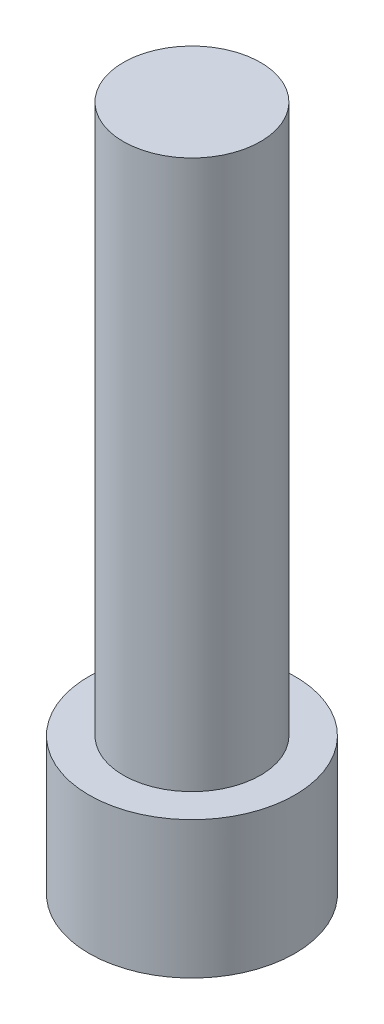
SolidWorks part; units mm, degrees
ref_plane "Front Plane" through (0, 0, 0) normal (0, 0, 1) x (1, 0, 0)
ref_plane "Top Plane" through (0, 0, 0) normal (0, 1, 0) x (1, 0, 0)
ref_plane "Right Plane" through (0, 0, 0) normal (1, 0, 0) x (0, 0, -1)
sketch "Sketch1" plane through (0, 0, 0) normal (0, 1, 0) x (1, 0, 0)
  line L1 (5.7735, 0) -> (2.8868, 5)
  line L2 (2.8868, 5) -> (-2.8868, 5)
  line L3 (-2.8868, 5) -> (-5.7735, 0)
  line L4 (-5.7735, 0) -> (-2.8868, -5)
  line L5 (-2.8868, -5) -> (2.8868, -5)
  line L6 (2.8868, -5) -> (5.7735, 0)
  circle A0 centre (0, 0) radius 5
  circle A1 centre (0, 0) radius 7.5
  circle A2 centre (0, 0) radius 5 construction
  point P4 (0, 0)
  dimension "D1" = 10
  dimension "D2" = 15
  dimension "D3" = 10
extrude "Boss-Extrude1" add sketch "Sketch1" along normal blind 40 contours A0 region at (0, 0, 0)
extrude "Boss-Extrude2" add sketch "Sketch1<3>" against normal blind 3 contours A0 L4 L5 | A0 L5 L6 | A0 L6 L1 | A0 L1 L2 | A0 L2 L3 | A1 L6 L5 L4 L3 L2 L1 | A0 L3 L4 | A0 region at (5.1678, 0, 0) region at (2.5839, 0, -4.4755) region at (0, 0, 0) region at (2.5839, 0, 4.4755) region at (-2.5839, 0, -4.4755) region at (-2.5839, 0, 4.4755) region at (-5.1678, 0, 0) region at (-7.2879, 0, 0)
sketch "Sketch1<3>" plane through (0, 0, 0) normal (0, 1, 0) x (1, 0, 0) same geometry as "Sketch1"
sketch "Sketch2" plane through (0, -3, 0) normal (0, -1, 0) x (1, 0, 0)
  line L1 (5.7735, 0) -> (2.8868, 5)
  line L2 (2.8868, 5) -> (-2.8868, 5)
  line L3 (-2.8868, 5) -> (-5.7735, 0)
  line L4 (-5.7735, 0) -> (-2.8868, -5)
  line L5 (-2.8868, -5) -> (2.8868, -5)
  line L6 (2.8868, -5) -> (5.7735, 0)
  circle A0 centre (0, 0) radius 5 construction
  circle A2 centre (0, 0) radius 7.5
  circle A3 centre (0, 0) radius 7.5
  point P1 (0, 0)
  dimension "D1" = 10
  dimension "D2" = 0
extrude "Boss-Extrude3" add sketch "Sketch2" along normal blind 7
